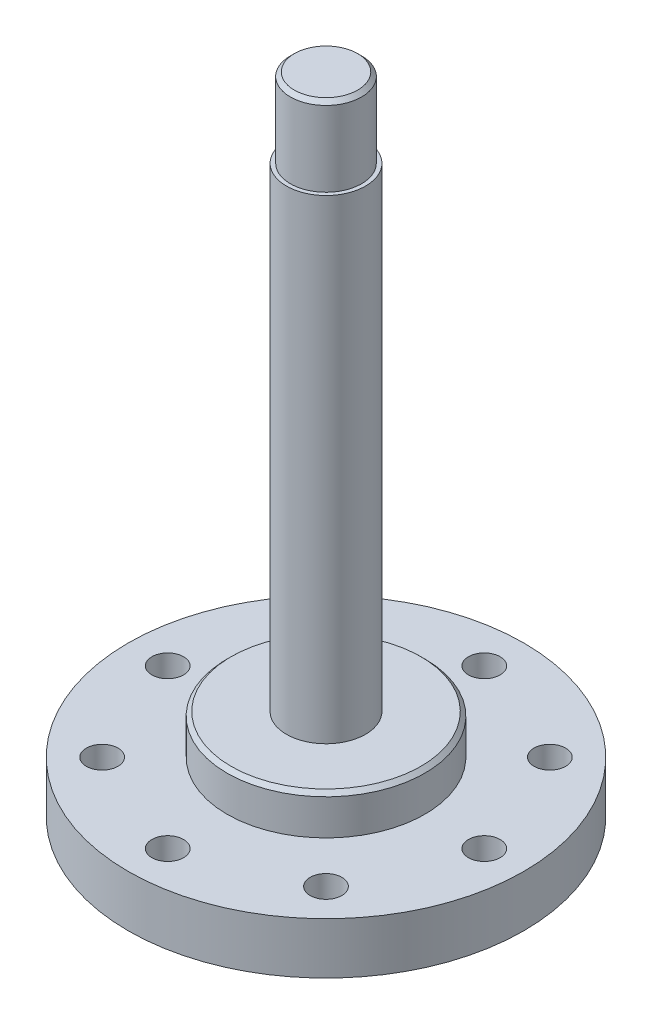
SolidWorks part; units mm, degrees
ref_plane "Front Plane" through (0, 0, 0) normal (0, 0, 1) x (1, 0, 0)
ref_plane "Top Plane" through (0, 0, 0) normal (0, 1, 0) x (1, 0, 0)
ref_plane "Right Plane" through (0, 0, 0) normal (1, 0, 0) x (0, 0, -1)
sketch "Sketch2" plane through (0, 0, 0) normal (1, 0, 0) x (0, 0, -1)
  line L0 (0, 0) -> (0, 163) construction
  line L1 (0, 0) -> (50, 0)
  line L2 (50, 0) -> (50, 13)
  line L3 (50, 13) -> (25, 13)
  line L4 (25, 13) -> (25, 23)
  line L5 (25, 23) -> (10, 23)
  line L6 (10, 23) -> (10, 143)
  line L7 (10, 143) -> (9, 143)
  line L8 (9, 143) -> (9, 163)
  line L9 (9, 163) -> (0, 163)
  line L10 (0, 163) -> (0, 0)
  point P7 (4.5, 163)
  dimension "D1" = 163
  dimension "D2" = 10
  dimension "D3" = 20
  dimension "D4" = 120
  dimension "D5" = 50
  dimension "D6" = 25
  dimension "D7" = 10
  dimension "D8" = 1
revolve "Revolve1" add sketch "Sketch2" angle 360 about L0
chamfer "Chamfer1" distance 1 angle 45 1 edges at (0, 163, -9)
chamfer "Chamfer2" distance 1 angle 45 1 edges at (0, 23, -25)
sketch "Sketch3" plane through (0, 0, 0) normal (0, -1, 0) x (1, 0, 0)
  line L0 (0, 0) -> (40, 0)
  circle A0 centre (0, 0) radius 40
  circle A1 centre (0, 0) radius 50
  circle A2 centre (0, 0) radius 50
  circle A3 centre (40, 0) radius 4
  circle A4 centre (28.2843, -28.2843) radius 4
  circle A5 centre (0, -40) radius 4
  circle A6 centre (-28.2843, -28.2843) radius 4
  circle A7 centre (-40, 0) radius 4
  circle A8 centre (-28.2843, 28.2843) radius 4
  circle A9 centre (0, 40) radius 4
  circle A10 centre (28.2843, 28.2843) radius 4
  dimension "D2" = 80
  dimension "D3" = 8
  dimension "D1" = 0
  dimension "D4" = 8
extrude "Cut-Extrude1" cut sketch "Sketch3" against normal through all contours A0 A8 | A0 A8 | A0 A6 | A0 A6 | A0 A5 | A0 A5 | A0 A4 | A0 A4 | A0 A3 L0 | L0 A3 A0 | A0 A3 | A0 A10 | A0 A10 | A0 A9 | A0 A9 | A7 region at (38.2668, 0, 1.6694) region at (38.2668, 0, -1.6694) region at (41.6611, 0, 0) region at (27.0587, 0, 27.0587) region at (29.4589, 0, 29.4589) region at (29.4589, 0, -29.4589) region at (27.0587, 0, -27.0587) region at (0, 0, 38.2668) region at (0, 0, 41.6611) region at (0, 0, -41.6611) region at (0, 0, -38.2668) region at (-27.0587, 0, 27.0587) region at (-29.4589, 0, 29.4589) region at (-29.4589, 0, -29.4589) region at (-27.0587, 0, -27.0587)
sketch "Sketch5" plane through (0, 163, 0) normal (0, 1, 0) x (1, 0, 0)
  line L0 (0, 7.7463) -> (0, 8)
  line L2 (0, 0) -> (0, 7.7463)
  line L5 (0, 0) -> (0, 5)
  line L6 (3, 5) -> (-3, 5)
  line L7 (-3, 5) -> (-3, 7.4162)
  line L8 (3, 5) -> (3, 7.4162)
  line L9 (-3, 7.4162) -> (-3, 8.4853)
  line L10 (3, 7.4162) -> (3, 8.4853)
  circle A1 centre (0, 0) radius 8
  circle A2 centre (0, 0) radius 8
  circle A3 centre (0, 0) radius 9
  circle A4 centre (0, 0) radius 9
  circle M5 centre (0, 0) radius 8
  dimension "D2" = 5
  dimension "D3" = 3
  dimension "D1" = 0
  dimension "D4" = 0
extrude "Cut-Extrude2" cut sketch "Sketch5" against normal blind 14 from offset 3 contours L7 L6 L2 L0 M5 | L6 L8 L0 L2 M5 | L10 A4 L9 M5 region at (-1.4484, 163, -6.4095) region at (1.4484, 163, -6.4095) region at (0, 163, -8.3162) offset against normal yes
sketch "Sketch6" plane through (0, 0, -5) normal (0, 0, -1) x (-1, 0, 0)
  line L0 (0, 160) -> (0, 146)
  line L1 (0, 153) -> (0, 158)
  line L2 (0, 148) -> (0, 158) construction
  line L3 (-2, 148) -> (-2, 158)
  line L4 (3, 160) -> (-3, 160)
  line L5 (-3, 160) -> (-3, 146)
  line L6 (-3, 146) -> (3, 146)
  line L7 (3, 146) -> (3, 160)
  line L8 (3, 160) -> (-3, 160)
  line L9 (-3, 160) -> (-3, 146)
  line L10 (-3, 146) -> (3, 146)
  line L11 (3, 146) -> (3, 160)
  line L12 (2, 148) -> (2, 158)
  arc A0 (-2, 148) -> (2, 148) centre (0, 148) ccw
  arc A1 (2, 158) -> (-2, 158) centre (0, 158) ccw
  point P9 (0, 153)
  line M5 (3, 160) -> (-3, 160)
  line M6 (-3, 160) -> (-3, 146)
  line M7 (-3, 146) -> (3, 146)
  line M8 (3, 146) -> (3, 160)
  dimension "D3" = 2
  dimension "D2" = 5
  dimension "D1" = 0
extrude "Boss-Extrude1" add sketch "Sketch6" along normal up to surface (3.775 mm away) contours A1 A0 L3 M5 M6 M7 | A1 L12 A0 M7 M8 M5 region at (2.3966, 153, -5) region at (-2.3966, 153, -5) up to face at (0, 162, 9)
